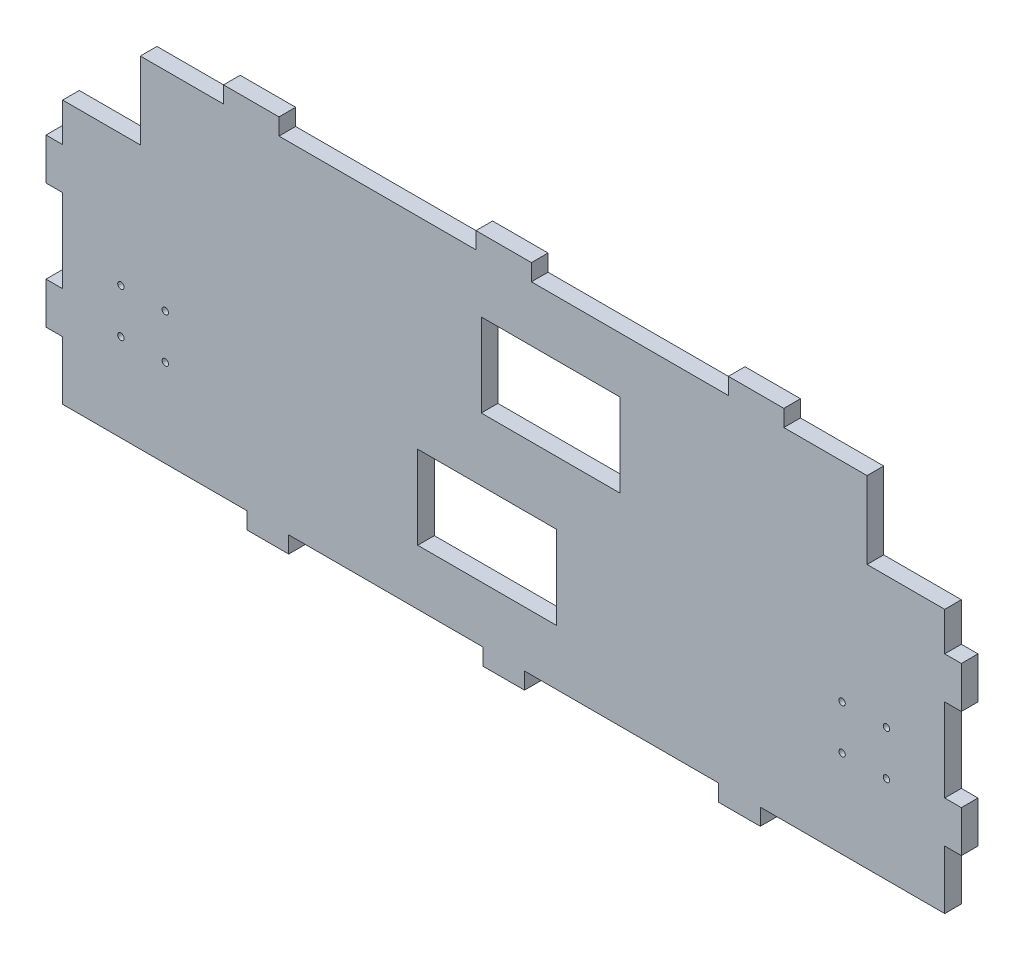
SolidWorks part; units mm, degrees
ref_plane "Plan de face" through (0, 0, 0) normal (0, 0, 1) x (1, 0, 0)
ref_plane "Plan de dessus" through (0, 0, 0) normal (0, 1, 0) x (1, 0, 0)
ref_plane "Plan de droite" through (0, 0, 0) normal (1, 0, 0) x (0, 0, -1)
sketch "Esquisse1" plane through (0, 0, 0) normal (0, 0, 1) x (1, 0, 0)
  line L0 (-159, 35) -> (-131, 35)
  line L1 (0, 102.0551) -> (0, -193.4247) construction
  line L2 (-159, 35) -> (-159, -60)
  line L3 (-159, -60) -> (159, -60)
  line L4 (159, 35) -> (159, -60)
  line L6 (131, 35) -> (131, 62.75)
  line L7 (131, 62.75) -> (-131, 62.75)
  line L8 (-131, 35) -> (-131, 62.75)
  line L9 (159, 35) -> (131, 35)
  line L10 (19, -10) -> (-31, -10)
  line L11 (19, -10) -> (19, -40)
  line L12 (19, -40) -> (-31, -40)
  line L13 (-31, -10) -> (-31, -40)
  line L14 (41.9165, 42.75) -> (-8.0835, 42.75)
  line L15 (41.9165, 42.75) -> (41.9165, 12.75)
  line L16 (41.9165, 12.75) -> (-8.0835, 12.75)
  line L17 (-8.0835, 42.75) -> (-8.0835, 12.75)
  dimension "D1" = 95
  dimension "D2" = 28
  dimension "D3" = 28
  dimension "D4" = 95
  dimension "D6" = 262
  dimension "D7" = 122.75
  dimension "D5" = 159
  dimension "D8" = 318
  dimension "D9" = 30
  dimension "D10" = 50
  dimension "D11" = 20
  dimension "D12" = 140
  dimension "D13" = 30
  dimension "D14" = 50
  dimension "D15" = 20
extrude "Boss.-Extru.1" add sketch "Esquisse1" along normal blind 6
sketch "Esquisse2" plane through (0, 0, 6) normal (0, 0, 1) x (1, 0, 0)
  line L0 (-159, -60) -> (159, -60) construction
  line L1 (-92.5, -60) -> (-77.5, -60)
  line L2 (-92.5, -60) -> (-92.5, -66)
  line L3 (-92.5, -66) -> (-77.5, -66)
  line L4 (-77.5, -60) -> (-77.5, -66)
  line L5 (-159, 35) -> (-159, -60) construction
  line L6 (-7.5, -60) -> (7.5, -60)
  line L7 (-7.5, -60) -> (-7.5, -66)
  line L8 (-7.5, -66) -> (7.5, -66)
  line L9 (7.5, -60) -> (7.5, -66)
  line L10 (77.5, -60) -> (92.5, -60)
  line L11 (77.5, -60) -> (77.5, -66)
  line L12 (77.5, -66) -> (92.5, -66)
  line L13 (92.5, -60) -> (92.5, -66)
  line L14 (176.2958, 0) -> (-249.7093, -3.2925) construction
  line L15 (0, 107.6082) -> (0, -117.4775) construction
  line L16 (-131, 35) -> (-159, 35) construction
  line L17 (-159, 21.09) -> (-165, 21.09)
  line L18 (-159, 21.09) -> (-159, 6.09)
  line L19 (-159, 6.09) -> (-165, 6.09)
  line L20 (-165, 21.09) -> (-165, 6.09)
  line L21 (-159, -23.91) -> (-165, -23.91)
  line L22 (-159, -23.91) -> (-159, -38.91)
  line L23 (-159, -38.91) -> (-165, -38.91)
  line L24 (-165, -23.91) -> (-165, -38.91)
  line L25 (165, -23.91) -> (165, -38.91)
  line L26 (159, -38.91) -> (165, -38.91)
  line L27 (159, -23.91) -> (159, -38.91)
  line L28 (159, -23.91) -> (165, -23.91)
  line L29 (165, 21.09) -> (165, 6.09)
  line L30 (159, 6.09) -> (165, 6.09)
  line L31 (159, 21.09) -> (159, 6.09)
  line L32 (159, 21.09) -> (165, 21.09)
  line L33 (131, 62.75) -> (-131, 62.75) construction
  line L34 (101, 62.75) -> (81, 62.75)
  line L35 (101, 62.75) -> (101, 68.75)
  line L36 (101, 68.75) -> (81, 68.75)
  line L37 (81, 62.75) -> (81, 68.75)
  line L38 (-131, 62.75) -> (-131, 35) construction
  line L39 (-81, 62.75) -> (-101, 62.75)
  line L40 (-81, 62.75) -> (-81, 68.75)
  line L41 (-81, 68.75) -> (-101, 68.75)
  line L42 (-101, 62.75) -> (-101, 68.75)
  line L43 (10, 62.75) -> (-10, 62.75)
  line L44 (10, 62.75) -> (10, 68.75)
  line L45 (10, 68.75) -> (-10, 68.75)
  line L46 (-10, 62.75) -> (-10, 68.75)
  line L47 (131, 35) -> (131, 62.75) construction
  dimension "D1" = 66.5
  dimension "D2" = 70
  dimension "D3" = 15
  dimension "D4" = 15
  dimension "D5" = 70
  dimension "D6" = 15
  dimension "D7" = 6
  dimension "D8" = 6
  dimension "D9" = 6
  dimension "D10" = 6
  dimension "D11" = 13.91
  dimension "D12" = 15
  dimension "D13" = 30
  dimension "D14" = 15
  dimension "D15" = 20
  dimension "D16" = 20
  dimension "D17" = 20
  dimension "D18" = 30
  dimension "D19" = 30
  dimension "D20" = 121
  dimension "D21" = 6
  dimension "D22" = 6
  dimension "D23" = 6
  dimension "D24" = 6
extrude "Boss.-Extru.2" add sketch "Esquisse2" against normal blind 6
sketch "Esquisse3" plane through (0, 0, 0) normal (0, 0, -1) x (-1, 0, 0)
  line L0 (159, -60) -> (92.5, -60) construction
  line L1 (159, 6.09) -> (159, -23.91) construction
  line L2 (0, 141.59) -> (0, -167.3887) construction
  circle A0 centre (138, -28.38) radius 1.15
  circle A1 centre (138, -12.38) radius 1.15
  circle A2 centre (122, -12.38) radius 1.15
  circle A3 centre (122, -28.38) radius 1.15
  circle A4 centre (-122, -28.38) radius 1.15
  circle A5 centre (-122, -12.38) radius 1.15
  circle A6 centre (-138, -12.38) radius 1.15
  circle A7 centre (-138, -28.38) radius 1.15
  dimension "D1" = 31.62
  dimension "D2" = 21
  dimension "D7" = 2.3
  dimension "D8" = 2.3
  dimension "D9" = 2.3
  dimension "D10" = 2.3
  dimension "D3" = 16
  dimension "D4" = 16
  dimension "D5" = 16
  dimension "D6" = 16
extrude "Enlèv. mat.-Extru.1" cut sketch "Esquisse3" against normal blind 6
equation "\"D5@Esquisse1\"=\"D8@Esquisse1\"/2"
